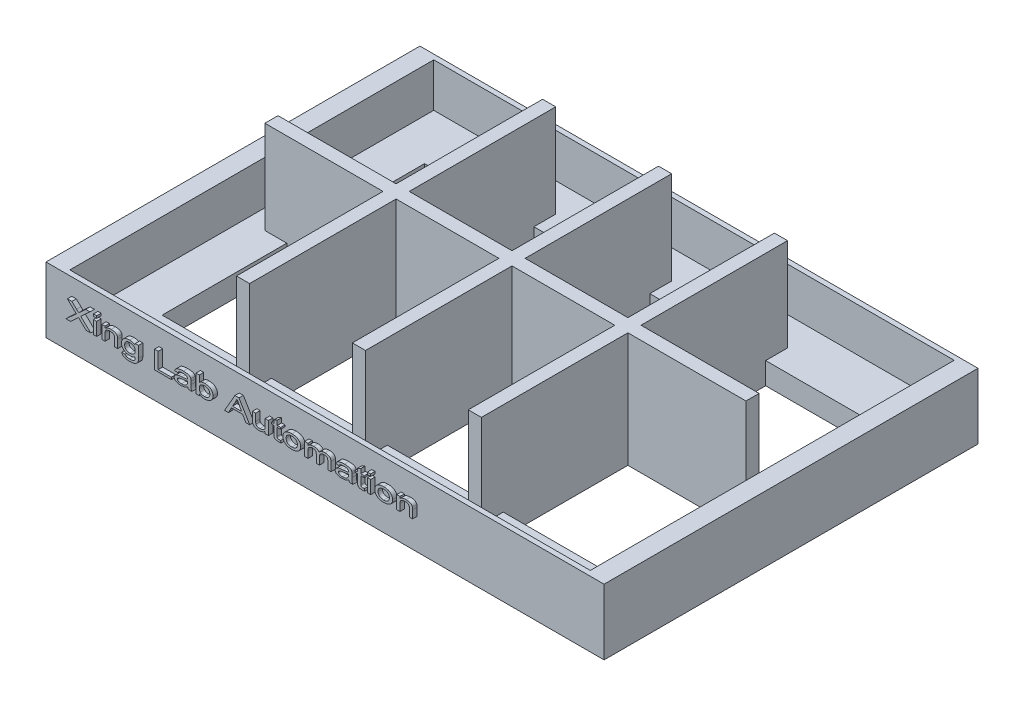
SolidWorks part; units mm, degrees
note: The reader was unsure of these and kept them because the rebuilt part matched: shared geometry of "草图1<4>", "草图1<11>".
ref_plane "前视基准面" through (0, 0, 0) normal (0, 0, 1) x (1, 0, 0)
ref_plane "上视基准面" through (0, 0, 0) normal (0, 1, 0) x (1, 0, 0)
ref_plane "右视基准面" through (0, 0, 0) normal (1, 0, 0) x (0, 0, -1)
other "Configuration Table"
sketch "草图1" plane through (0, 0, 0) normal (0, 1, 0) x (1, 0, 0)
  line L0 (-59.5, 42.75) -> (-59.5, -42.7501)
  line L1 (-63.8, -42.75) -> (63.8, -42.75)
  line L3 (-63.8, 42.75) -> (63.8, 42.75)
  line L4 (63.8, -42.75) -> (63.8, 42.75)
  line L5 (-63.8, -42.75) -> (63.8, 42.75) construction
  line L6 (-63.8, 42.75) -> (63.8, -42.75) construction
  line L8 (-63.8, 42.75) -> (-63.8, -42.75)
  line L15 (-59.5, -41.6001) -> (59.5, -41.6001)
  line L17 (-59.5, -42.7501) -> (59.5, -42.7501)
  line L21 (-59.5, 41.6049) -> (59.5, 41.6049)
  line L23 (-50, -30) -> (50, -30)
  line L24 (-50, -30) -> (-50, 30)
  line L25 (-50, 30) -> (50, 30)
  line L26 (50, -30) -> (50, 30)
  line L27 (-50, -30) -> (50, 30) construction
  line L28 (-50, 30) -> (50, -30) construction
  line L30 (1.5, -30) -> (1.5, 30)
  line L32 (-1.5, -30) -> (-1.5, 30)
  line L33 (1.5, -30) -> (-1.5, 30) construction
  line L34 (1.5, 30) -> (-1.5, -30) construction
  line L35 (50, 1.5) -> (-50, 1.5)
  line L37 (50, -1.5) -> (-50, -1.5)
  line L39 (50, 1.5) -> (-50, -1.5) construction
  line L40 (50, -1.5) -> (-50, 1.5) construction
  line L41 (59.5, 42.75) -> (59.5, -42.7501)
  line L43 (-50, 1.5) -> (50, 1.5)
  line L44 (-50, 1.5) -> (-50, -1.5)
  line L45 (-50, -1.5) -> (50, -1.5)
  line L46 (50, 1.5) -> (50, -1.5)
  line L47 (-50, 1.5) -> (-55, 1.5)
  line L48 (-50, 1.5) -> (-50, -1.5)
  line L49 (-50, -1.5) -> (-55, -1.5)
  line L50 (-55, 1.5) -> (-55, -1.5)
  line L51 (50, 1.5) -> (55, 1.5)
  line L52 (50, 1.5) -> (50, -1.5)
  line L53 (50, -1.5) -> (55, -1.5)
  line L54 (55, 1.5) -> (55, -1.5)
  line L55 (-1.5, 30) -> (1.5, 30)
  line L56 (-1.5, 30) -> (-1.5, 35)
  line L57 (-1.5, 35) -> (1.5, 35)
  line L58 (1.5, 30) -> (1.5, 35)
  line L59 (1.5, -30) -> (-1.5, -30)
  line L60 (1.5, -30) -> (1.5, -35)
  line L61 (1.5, -35) -> (-1.5, -35)
  line L62 (-1.5, -30) -> (-1.5, -35)
  line L63 (-25, -35) -> (-28, -35)
  line L64 (-25, -35) -> (-25, 35)
  line L65 (-25, 35) -> (-28, 35)
  line L66 (-28, -35) -> (-28, 35)
  line L67 (25, 35) -> (28, 35)
  line L68 (25, 35) -> (25, -35)
  line L69 (25, -35) -> (28, -35)
  line L70 (28, 35) -> (28, -35)
  point P0 (0, 0)
  point P18 (0, 0)
  point P23 (0, 0)
  point P28 (0, 0)
  dimension "D1" = 127.6
  dimension "D2" = 85.5
  dimension "D7" = 119
  dimension "D8" = 1.15
  dimension "D9" = 60
  dimension "D10" = 100
  dimension "D11" = 100
extrude "凸台-拉伸2" add sketch "草图1" along normal blind 5
extrude "凸台-拉伸3" add sketch "草图1<4>" along normal blind 15
sketch "草图1<4>" plane through (0, 0, 0) normal (0, 1, 0) x (1, 0, 0) same geometry as "草图1"
sketch "草图2" plane through (0, 0, 42.75) normal (0, 0, 1) x (1, 0, 0)
  text T0 "Xing Lab Automation" font "Helvetica" height in points 16
extrude "凸台-拉伸4" add sketch "草图2" along normal blind 1
extrude "凸台-拉伸5" add sketch "草图1<11>" along normal blind 26.25 contours L47 L50 L49 L24 | L37 L66 L35 L24 | L66 L45 L64 L43 | L66 L43 L64 L25 | L66 L25 L64 L65 | L25 L58 L57 L56 | L37 L30 L35 L32 | L64 L37 L32 L35 | L70 L43 L68 L45 | L68 L43 L30 L45 | L35 L30 L25 L32 | L70 L25 L68 L43 | L70 L67 L68 L25 | L35 L70 L37 L26 | L54 L51 L26 L53 | L70 L45 L68 L23 | L70 L23 L68 L69 | L23 L62 L61 L60 | L30 L37 L32 L23 | L66 L23 L64 L45 | L66 L63 L64 L23
sketch "草图1<11>" plane through (0, 0, 0) normal (0, 1, 0) x (1, 0, 0) same geometry as "草图1"
